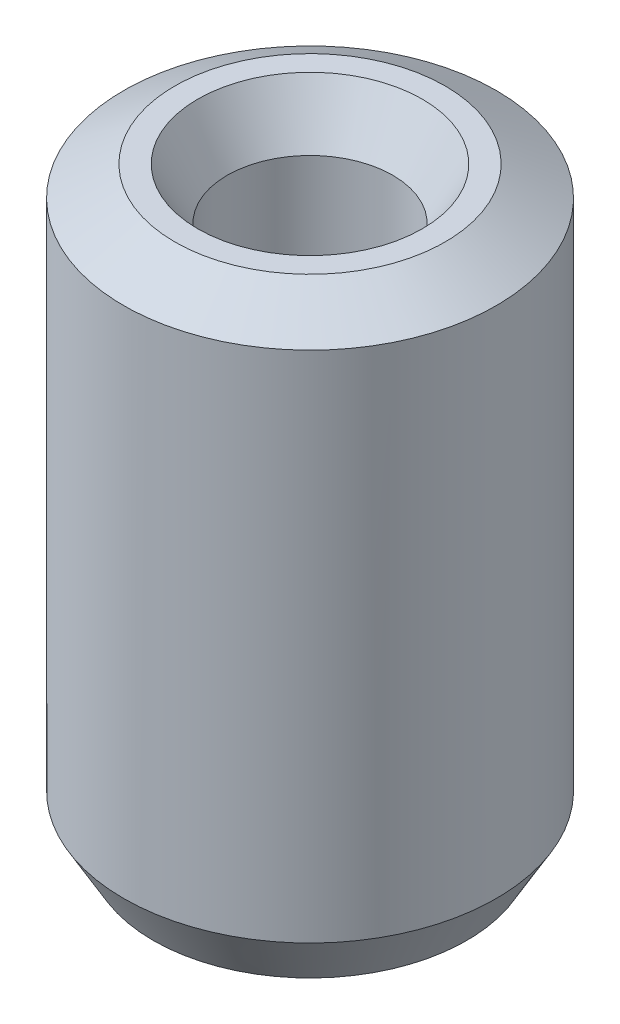
SolidWorks part; units mm, degrees
ref_plane "Front Plane" through (0, 0, 0) normal (0, 0, 1) x (1, 0, 0)
ref_plane "Top Plane" through (0, 0, 0) normal (0, 1, 0) x (1, 0, 0)
ref_plane "Right Plane" through (0, 0, 0) normal (1, 0, 0) x (0, 0, -1)
sketch "Sketch1" plane through (0, 0, 0) normal (0, 1, 0) x (1, 0, 0)
  circle A0 centre (0, 0) radius 7.5
  dimension "SLEEVE_OD" = 15
extrude "Boss-Extrude1" add sketch "Sketch1" along normal blind 23.9167
sketch "Sketch2" plane through (0, 0, 0) normal (0, 1, 0) x (1, 0, 0)
  circle A0 centre (0, 0) radius 3.3321
  dimension "BORE_D" = 6.6641
extrude "Cut-Extrude1" cut sketch "Sketch2" along normal through all
chamfer "Chamfer1" distance 1.1889 angle 60 4 edges at (0, 23.9167, 3.3321) (0, 0, 3.3321) (0, 0, 7.5) (0, 23.9167, 7.5) first distance on face at (0, 23.9167, 3.3321) first distance on face at (0, 0, 3.3321) first distance on face at (0, 23.9167, 7.5)
